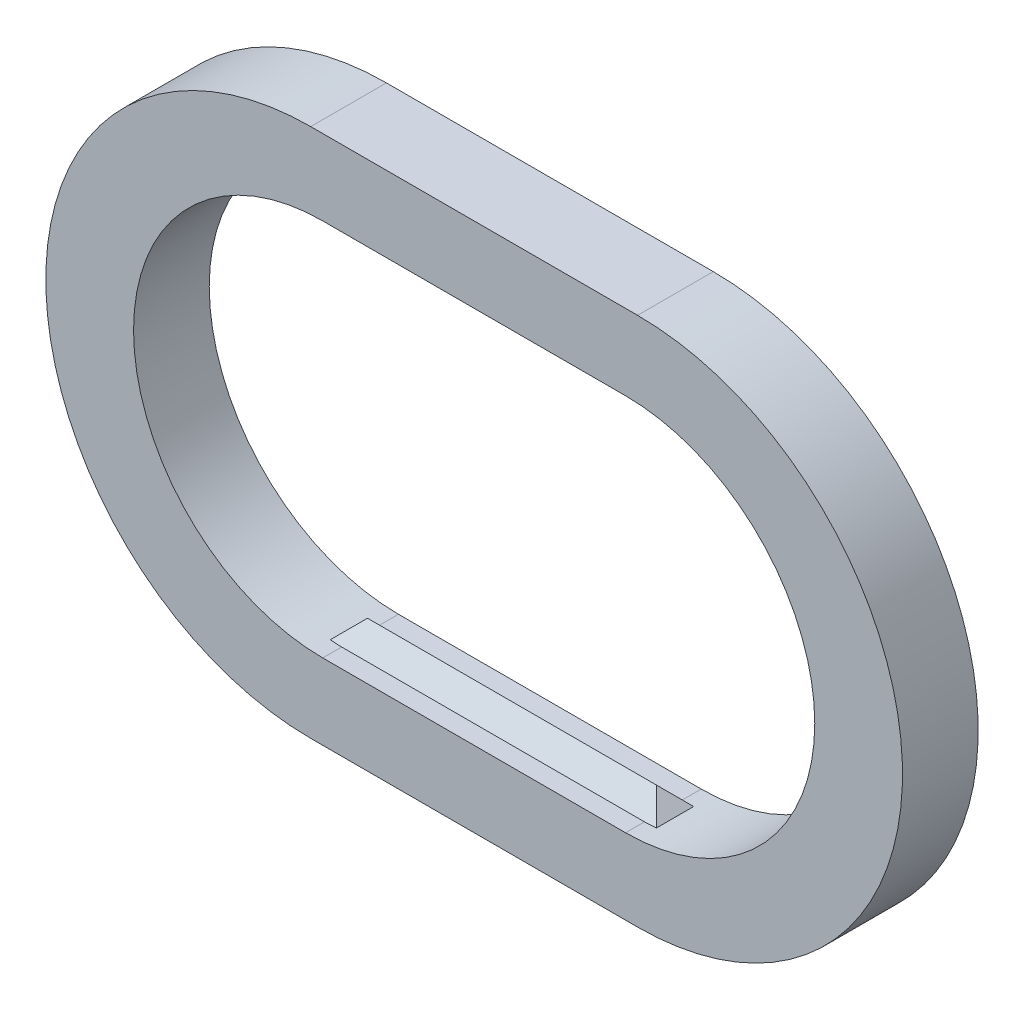
SolidWorks part; units mm, degrees
ref_plane "Front Plane" through (0, 0, 0) normal (0, 0, 1) x (1, 0, 0)
ref_plane "Top Plane" through (0, 0, 0) normal (0, 1, 0) x (1, 0, 0)
ref_plane "Right Plane" through (0, 0, 0) normal (1, 0, 0) x (0, 0, -1)
sketch "Sketch1" plane through (0, 0, 0) normal (0, 0, 1) x (1, 0, 0)
  line L0 (20.2442, 3.9156) -> (28.2442, 3.9156) construction
  line L1 (20.2442, 8.9156) -> (28.2442, 8.9156)
  line L2 (20.2442, -1.0844) -> (28.2442, -1.0844)
  line L3 (19.9257, 3.9156) -> (28.5627, 3.9156) construction
  line L4 (19.9257, 10.9156) -> (28.5627, 10.9156)
  line L5 (19.9257, -3.0844) -> (28.5627, -3.0844)
  line L6 (11.1132, 3.9156) -> (36.2646, 3.9156) construction
  arc A0 (20.2442, 8.9156) -> (20.2442, -1.0844) centre (20.2442, 3.9156) ccw
  arc A1 (28.2442, -1.0844) -> (28.2442, 8.9156) centre (28.2442, 3.9156) ccw
  arc A2 (19.9257, 10.9156) -> (19.9257, -3.0844) centre (19.9257, 3.9156) ccw
  arc A3 (28.5627, -3.0844) -> (28.5627, 10.9156) centre (28.5627, 3.9156) ccw
  point P2 (24.2442, 3.9156)
  point P9 (24.2442, 3.9156)
  point P16 (15.2442, 3.9156)
  point P17 (33.2442, 3.9156)
  dimension "D1" = 8
  dimension "D2" = 10
  dimension "D3" = 0.3185
  dimension "D4" = 0.3185
  dimension "D5" = 2
  dimension "D6" = 18
extrude "BaseBoss-Extrude1" add sketch "Sketch1" along normal blind 2
sketch "Sketch3" plane through (0, 8.9156, 0) normal (0, -1, 0) x (1, 0, 0)
  line L0 (19.9257, 2) -> (19.9257, 0) construction
  line L1 (19.9257, 1.4) -> (28.5627, 1.4)
  line L2 (19.9257, 1.4) -> (19.9257, 0.4)
  line L3 (19.9257, 0.4) -> (28.5627, 0.4)
  line L4 (28.5627, 1.4) -> (28.5627, 0.4)
  line L5 (28.5627, 2) -> (28.5627, 0) construction
  line L6 (19.9257, 0) -> (28.5627, 0) construction
  dimension "D1" = 1
  dimension "D2" = 0.4
extrude "Boss-Extrude1" add sketch "Sketch3" along normal blind 0.5
sketch "Sketch4" plane through (0, -1.0844, 0) normal (0, 1, 0) x (1, 0, 0)
  line L0 (19.9257, -2) -> (19.9257, 0) construction
  line L1 (19.9257, -0.5) -> (28.5627, -0.5)
  line L2 (19.9257, -0.5) -> (19.9257, -1.5)
  line L3 (19.9257, -1.5) -> (28.5627, -1.5)
  line L4 (28.5627, -0.5) -> (28.5627, -1.5)
  line L5 (28.5627, -2) -> (28.5627, 0) construction
  line L6 (28.5627, -2) -> (19.9257, -2) construction
  dimension "D1" = 0.5
  dimension "D2" = 1
extrude "Boss-Extrude2" add sketch "Sketch4" along normal blind 0.5
chamfer "Chamfer1" distance 0.5 angle 45 4 edges at (28.5627, -0.5844, 1) (19.9257, -0.5844, 1) (28.5627, 8.4156, 0.9) (19.9257, 8.4156, 0.9)
chamfer "Chamfer2" distance 0.5 angle 45 4 edges at (24.2442, -0.5844, 0.5) (24.2442, 8.4156, 0.4) (24.2442, 8.4156, 1.4) (24.2442, -0.5844, 1.5)
equation "\"HoleLength\"= 6mm"
equation "\"D1@Sketch1\"=\"HoleLength\" + \"WallThickness\"*2"
equation "\"HoleWidth\"= 8mm"
equation "\"D2@Sketch1\"=\"HoleWidth\" + \"WallThickness\"*2 "
equation "\"LipWidth\"= 2mm"
equation "\"D3@Sketch1\"=\"LipWidth\"/6.28"
equation "\"D4@Sketch1\"=\"LipWidth\"/6.28"
equation "\"D5@Sketch1\"=\"LipWidth\""
equation "\"LipDepth\"= 2mm"
equation "\"HoleDepth\"= 10mm + \"LipDepth\""
equation "\"D1@BaseBoss-Extrude1\" = \"LipDepth\""
equation "\"WallThickness\"= 1mm"
equation "\"D1@Sketch3\"=\"LipDepth\"/2"
equation "\"D2@Sketch3\"=\"LipDepth\"/5"
equation "\"D1@Boss-Extrude1\"=\"WallThickness\"/2"
equation "\"D1@Sketch4\"=\"LipDepth\"/4"
equation "\"D2@Sketch4\"=\"LipDepth\"/2"
equation "\"D1@Boss-Extrude2\"=\"WallThickness\"/2"
equation "\"D1@Chamfer1\"=\"WallThickness\"/2"
equation "\"D1@Chamfer2\"=\"WallThickness\"/2"
